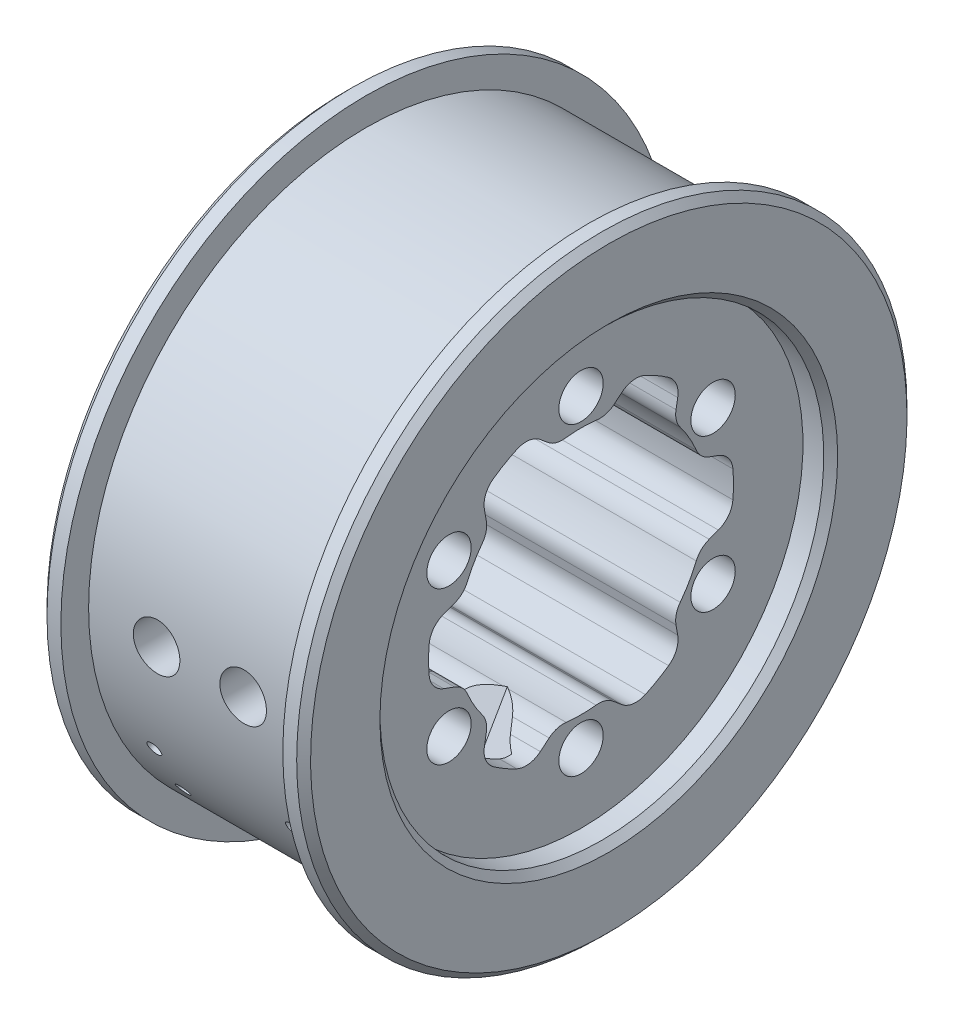
SolidWorks part; units mm, degrees
ref_plane "Front Plane" through (0, 0, 0) normal (0, 0, 1) x (1, 0, 0)
ref_plane "Top Plane" through (0, 0, 0) normal (0, 1, 0) x (1, 0, 0)
ref_plane "Right Plane" through (0, 0, 0) normal (1, 0, 0) x (0, 0, -1)
sketch "Sketch1" plane through (0, 0, 0) normal (0, 0, 1) x (1, 0, 0)
  line L0 (0, 0) -> (0, 31.75)
  line L1 (0, 31.75) -> (12.7, 31.75)
  line L2 (12.7, 31.75) -> (12.7, 34.925)
  line L3 (12.7, 34.925) -> (15.0812, 34.925)
  line L4 (15.0812, 34.925) -> (15.0813, 0)
  line L5 (15.0813, 0) -> (0, 0)
  dimension "D1" = 12.7
  dimension "D2" = 2.3813
  dimension "D3" = 3.175
  dimension "D4" = 31.75
revolve "Revolve1" add sketch "Sketch1" angle 360 about L5
sketch "Sketch2" plane through (15.0813, 0, 0) normal (1, 0, 0) x (0, 0, -1)
  line L0 (14.6656, 4.0824) -> (15.7207, 3.6983)
  line L1 (14.6656, -4.0824) -> (15.7207, -3.6983)
  line L2 (0, 0) -> (25.6394, 0) construction
  line L3 (3.6486, -14.6171) -> (4.6575, -15.4637)
  line L4 (10.8682, -10.6596) -> (11.0632, -11.7654)
  line L5 (-10.8345, -10.4683) -> (-11.0632, -11.7654)
  line L6 (-3.6486, -14.6171) -> (-4.6575, -15.4637)
  line L7 (-14.4831, 4.1488) -> (-15.7207, 3.6983)
  line L8 (-14.4831, -4.1488) -> (-15.7207, -3.6983)
  line L9 (-3.7974, 14.7419) -> (-4.6575, 15.4637)
  line L10 (-10.8345, 10.4683) -> (-11.0632, 11.7654)
  line L11 (10.8682, 10.6596) -> (11.0632, 11.7654)
  line L12 (3.7974, 14.7419) -> (4.6575, 15.4637)
  circle A0 centre (0, 0) radius 17.4498 construction
  circle A1 centre (0, 17.4498) radius 2.54
  circle A2 centre (15.112, 8.7249) radius 2.54
  circle A3 centre (15.112, -8.7249) radius 2.54
  circle A4 centre (0, -17.4498) radius 2.54
  circle A5 centre (-15.112, -8.7249) radius 2.54
  circle A6 centre (-15.112, 8.7249) radius 2.54
  circle A7 centre (0, 0) radius 14.2875 construction
  arc A9 (17.3822, 1.5349) -> (17.3822, -1.5349) centre (0, 0) cw
  arc A11 (10.0204, -14.2859) -> (7.3618, -15.8209) centre (0, 0) cw
  arc A12 (-7.3618, -15.8209) -> (-10.0204, -14.2859) centre (0, 0) cw
  arc A13 (-17.3822, -1.5349) -> (-17.3822, 1.5349) centre (0, 0) cw
  arc A14 (-10.0204, 14.2859) -> (-7.3618, 15.8209) centre (0, 0) cw
  arc A15 (7.3618, 15.8209) -> (10.0204, 14.2859) centre (0, 0) cw
  arc A16 (11.3516, -8.6761) -> (13.1895, -5.4927) centre (0, 0) ccw
  arc A18 (-1.709, -14.0414) -> (1.709, -14.0414) centre (0, 0) ccw
  arc A19 (-13.0148, -5.5407) -> (-11.3057, -8.5008) centre (0, 0) ccw
  arc A20 (-11.3057, 8.5008) -> (-13.0148, 5.5407) centre (0, 0) ccw
  arc A21 (1.8379, 14.1688) -> (-1.8379, 14.1688) centre (0, 0) ccw
  arc A22 (13.1895, 5.4927) -> (11.3516, 8.6761) centre (0, 0) ccw
  arc A23 (13.1895, 5.4927) -> (14.6656, 4.0824) centre (15.5343, 6.4692) ccw
  arc A24 (11.3516, 8.6761) -> (10.8682, 10.6596) centre (13.3696, 10.2185) cw
  arc A25 (11.0632, 11.7654) -> (10.0204, 14.2859) centre (8.5618, 12.2065) ccw
  arc A26 (7.3618, 15.8209) -> (4.6575, 15.4637) centre (6.2902, 13.518) ccw
  arc A27 (3.7974, 14.7419) -> (1.8379, 14.1688) centre (2.1647, 16.6877) cw
  arc A28 (-1.8379, 14.1688) -> (-3.7974, 14.7419) centre (-2.1647, 16.6877) cw
  arc A29 (-4.6575, 15.4637) -> (-7.3618, 15.8209) centre (-6.2902, 13.518) ccw
  arc A30 (-10.0204, 14.2859) -> (-11.0632, 11.7654) centre (-8.5618, 12.2065) ccw
  arc A31 (-10.8345, 10.4683) -> (-11.3057, 8.5008) centre (-13.3359, 10.0272) cw
  arc A32 (-13.0148, 5.5407) -> (-14.4831, 4.1488) centre (-15.3518, 6.5356) cw
  arc A33 (-15.7207, 3.6983) -> (-17.3822, 1.5349) centre (-14.852, 1.3115) ccw
  arc A34 (-17.3822, -1.5349) -> (-15.7207, -3.6983) centre (-14.852, -1.3115) ccw
  arc A35 (-14.4831, -4.1488) -> (-13.0148, -5.5407) centre (-15.3518, -6.5356) cw
  arc A36 (-11.3057, -8.5008) -> (-10.8345, -10.4683) centre (-13.3359, -10.0272) cw
  arc A37 (-11.0632, -11.7654) -> (-10.0204, -14.2859) centre (-8.5618, -12.2065) ccw
  arc A38 (-7.3618, -15.8209) -> (-4.6575, -15.4637) centre (-6.2902, -13.518) ccw
  arc A39 (-3.6486, -14.6171) -> (-1.709, -14.0414) centre (-2.0159, -16.5628) cw
  arc A40 (1.709, -14.0414) -> (3.6486, -14.6171) centre (2.0159, -16.5628) cw
  arc A41 (4.6575, -15.4637) -> (7.3618, -15.8209) centre (6.2902, -13.518) ccw
  arc A42 (10.0204, -14.2859) -> (11.0632, -11.7654) centre (8.5618, -12.2065) ccw
  arc A43 (10.8682, -10.6596) -> (11.3516, -8.6761) centre (13.3696, -10.2185) cw
  arc A44 (13.1895, -5.4927) -> (14.6656, -4.0824) centre (15.5343, -6.4692) cw
  arc A45 (15.7207, -3.6983) -> (17.3822, -1.5349) centre (14.852, -1.3115) ccw
  arc A46 (17.3822, 1.5349) -> (15.7207, 3.6983) centre (14.852, 1.3115) ccw
  point P18 (0, 0)
  point P45 (0, 0)
  point P52 (13.5661, 4.4825)
  point P61 (2.9011, 13.9899)
  point P92 (13.5661, -4.4825)
  point P95 (17.1585, -3.175)
  point P98 (17.1585, 3.175)
  dimension "D1" = 34.8996
  dimension "D2" = 5.08
  dimension "D4" = 28.575
  dimension "D5" = 20
  dimension "D7" = 6.35
  dimension "D9" = 2.54
  dimension "D10" = 2.54
  dimension "D6" = 20
  dimension "D3" = 6
  dimension "D8" = 6
mirror "Mirror3" about plane through (0, 0, 0) normal (-1, 0, 0) of "Revolve1"
extrude "Cut-Extrude3" cut sketch "Sketch2" against normal through all
sketch "Sketch3" plane through (15.0813, 0, 0) normal (1, 0, 0) x (0, 0, -1)
  circle A0 centre (0, 0) radius 25.4
  dimension "D1" = 50.8
extrude "Cut-Extrude4" cut sketch "Sketch3" against normal blind 3.175
sketch "Sketch4" plane through (-15.0813, 0, 0) normal (-1, 0, 0) x (0, 0, 1)
  circle A0 centre (0, 0) radius 25.4
  dimension "D1" = 50.8
extrude "Cut-Extrude5" cut sketch "Sketch4" against normal blind 3.048 contours A0
chamfer "Chamfer1" distance 0.7937 angle 45 4 edges at (-15.0813, -25.4, 0) (-15.0812, 34.925, 0) (15.0812, 34.925, 0) (15.0813, 25.4, 0)
ref_plane "Plane2" through (0, 0, 17.3822) normal (0, 0, 1) x (1, 0, 0)
ref_plane "Plane3" through (0, -15.0534, 8.6911) normal (0, -0.866, 0.5) x (-1, 0, 0)
sketch "Sketch7" plane through (0, 0, 17.3822) normal (0, 0, 1) x (1, 0, 0)
  line L1 (-4.9213, 5.6092) -> (-9.779, 2.8046)
  line L2 (-9.779, 2.8046) -> (-9.779, -2.8046)
  line L3 (-9.779, -2.8046) -> (-4.9213, -5.6092)
  line L4 (-4.9213, -5.6092) -> (-0.0635, -2.8046)
  line L6 (-0.0635, 2.8046) -> (-4.9213, 5.6092)
  line L7 (4.9848, 5.7192) -> (-0.0635, 2.8046)
  line L9 (-0.0635, -2.8046) -> (4.9848, -5.7192)
  line L10 (4.9848, -5.7192) -> (9.9378, -2.8596)
  line L11 (9.9378, -2.8596) -> (9.9377, 2.8596)
  line L12 (9.9377, 2.8596) -> (4.9848, 5.7192)
  line L13 (-12.0333, 1.5349) -> (-12.0333, -1.5349) construction
  line L14 (11.9062, -1.5349) -> (-12.0333, -1.5349) construction
  line L15 (-0.0635, -3.0186) -> (-0.0635, 2.7006) [skipped]
  line L16 (0.0318, 2.8596) -> (0.0318, -2.8596) [skipped]
  circle A0 centre (-4.9213, 0) radius 4.8577 construction
  circle A1 centre (4.9848, 0) radius 4.953 construction
  point P12 (-0.0635, -1.5349)
  point P23 (-12.0333, 0)
  dimension "D1" = 9.906
  dimension "D2" = 9.906
extrude "Cut-Extrude6" cut sketch "Sketch7" along normal blind 14.605 from offset 5.08 offset against normal yes
sketch "Sketch10" plane through (0, 0, 26.9072) normal (0, 0, -1) x (-1, 0, 0)
  line L0 (-4.9848, 5.7192) -> (-4.9848, -5.7192) construction
  line L1 (4.9213, 5.6092) -> (4.9213, -5.6092) construction
  circle A0 centre (-4.9848, 0) radius 2.667
  circle A1 centre (4.9213, 0) radius 2.667
  dimension "D1" = 5.334
extrude "Cut-Extrude9" cut sketch "Sketch10" against normal through all
pattern_circular "CirPattern1" count 2 every 60 about axis through (15.0813, 0, 0) along (1, 0, 0) of "Cut-Extrude6", "Cut-Extrude9"
ref_plane "Plane4" through (0, -7.0207, 12.1603) normal (0, -0.5, 0.866) x (1, 0, 0)
sketch "Sketch11" plane through (0, -7.0207, 12.1603) normal (0, -0.5, 0.866) x (1, 0, 0)
  line L4 (-12.7, -31.75) -> (-12.7, 31.75) construction
  line L5 (12.7, 31.75) -> (12.7, -31.75) construction
  line L6 (5.294, 1.709) -> (11.9062, 1.709) construction
  line L7 (5.294, -1.709) -> (11.9062, -1.709) construction
  circle A0 centre (-7.9375, -3.2965) radius 0.7937
  circle A1 centre (-7.9375, 3.2965) radius 0.7937
  circle A2 centre (7.9375, 3.2965) radius 0.7938
  circle A3 centre (7.9375, -3.2965) radius 0.7938
  point P2 (-9.525, 2.1045)
  point P3 (-9.525, -2.2677)
  point P6 (0, 0)
  point P7 (0, 0)
  point P10 (9.525, 2.7293)
  point P11 (0, 0)
  point P14 (9.525, -2.5645)
  point P15 (0, 0)
  point P20 (0, 0)
  point P21 (0, 0)
  point P22 (9.525, 1.709)
  point P23 (0, 0)
  point P24 (0, 0)
  dimension "D1" = 1.5875
  dimension "D2" = 4.7625
  dimension "D3" = 4.7625
  dimension "D4" = 1.5875
  dimension "D5" = 1.5875
extrude "Cut-Extrude10" cut sketch "Sketch11" along normal through all
